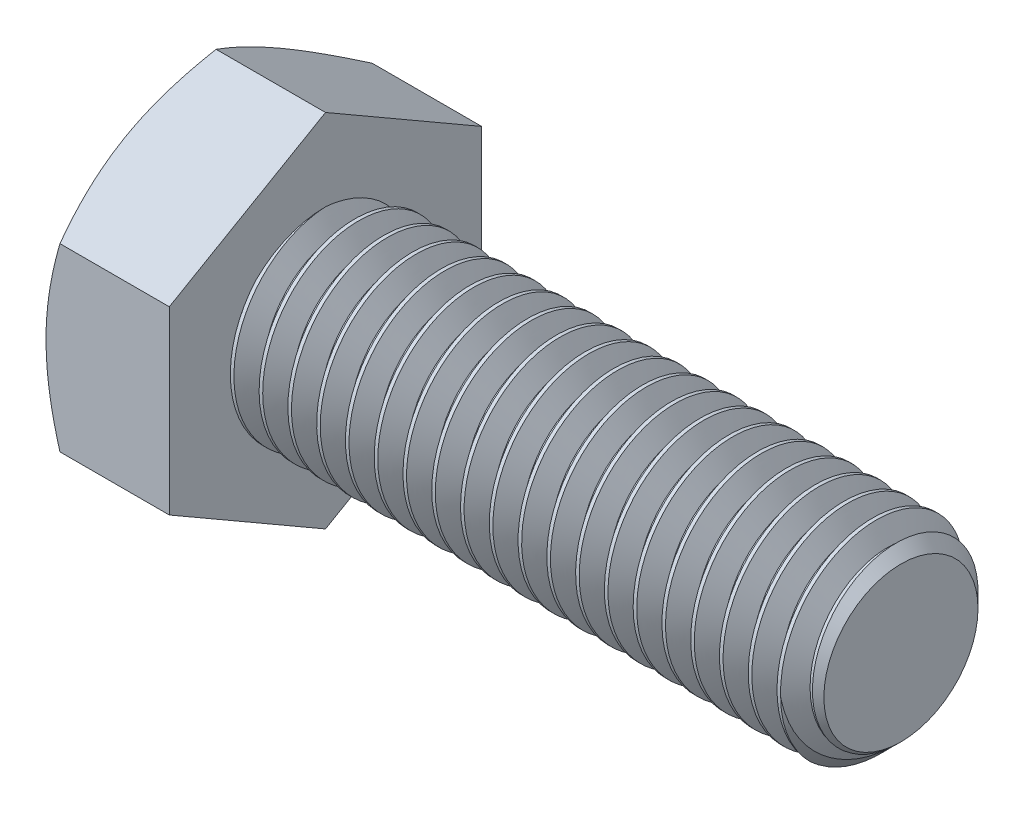
SolidWorks part; units mm, degrees
ref_plane "Front Plane" through (0, 0, 0) normal (0, 0, 1) x (1, 0, 0)
ref_plane "Top Plane" through (0, 0, 0) normal (0, 1, 0) x (1, 0, 0)
ref_plane "Right Plane" through (0, 0, 0) normal (1, 0, 0) x (0, 0, -1)
sketch "Sketch1" plane through (0, 0, 0) normal (0, 0, 1) x (1, 0, 0)
  line L0 (-21.25, 0) -> (21.25, 0) construction
  line L1 (-13.75, 9.5) -> (-13.75, -9.5) construction
  line L2 (-21.25, 9.5) -> (-21.25, -9.5) construction
  line L3 (21.25, 6) -> (21.25, -6) construction
  point P8 (15.125, -6)
  dimension "Thread Dia" = 12
  dimension "Hex" = 19
  dimension "Head Ht" = 7.5
  dimension "Length" = 35
  dimension "D1" = 6.125
ref_plane "Plane2" through (21.25, 0, 0) normal (1, 0, 0) x (0, 0, -1)
sketch "Sketch2" plane through (21.25, 0, 0) normal (1, 0, 0) x (0, 0, -1)
  circle A0 centre (0, 0) radius 6
extrude "Boss-Extrude1" add sketch "Sketch2" against normal up to vertex (35 mm away) up to point (-13.75, -9.5, 0)
sketch "Sketch4" plane through (21.25, 0, 0) normal (1, 0, 0) x (0, 0, -1)
  circle A1 centre (0, 0) radius 6
  circle A2 centre (0, 0) radius 6
  dimension "D1" = 0
curve "Helix/Spiral1" pitch 1.75 height 36.75 turns 21 parameters "Pitch"=1.75
chamfer "Chamfer1" distance 1.3125 angle 45 1 edges at (21.25, 0, -6)
sketch "Sketch5" plane through (0, 0, 0) normal (0, 0, 1) x (1, 0, 0)
  line L0 (21.25, 6) -> (21.9063, 4.8633)
  line L1 (21.9063, 4.8633) -> (22.125, 4.8633)
  line L2 (22.125, 4.8633) -> (22.7813, 6)
  line L3 (21.25, 6) -> (22.7813, 6)
  line L4 (22.0156, 4.8633) -> (22.0156, 6) construction
  line L5 (21.5781, 5.4317) -> (22.4531, 5.4317) construction
  line L6 (21.25, -6) -> (21.25, 6) construction
  dimension "D1" = 60
  dimension "D2" = 0.2188
  dimension "D3" = 0.875
sweep "Cut-Sweep1" cut profiles "Sketch5" path "Helix/Spiral1" align with end faces yes
sketch "Sketch3" plane through (-13.75, 0, 0) normal (-1, 0, 0) x (0, 0, 1)
  line L0 (0, 9.5) -> (0, -9.5) construction
  line L1 (-9.5, -5.4848) -> (0, -10.9697)
  line L2 (0, -10.9697) -> (9.5, -5.4848)
  line L3 (9.5, -5.4848) -> (9.5, 5.4848)
  line L4 (9.5, 5.4848) -> (0, 10.9697)
  line L5 (0, 10.9697) -> (-9.5, 5.4848)
  line L6 (-9.5, 5.4848) -> (-9.5, -5.4848)
  circle A0 centre (0, 0) radius 9.5 construction
extrude "Boss-Extrude2" add sketch "Sketch3" along normal up to vertex (7.5 mm away) up to point (-21.25, -9.5, 0)
sketch "Sketch6" plane through (-21.25, 0, 0) normal (-1, 0, 0) x (0, 0, 1)
  circle A0 centre (0, 0) radius 9.5 construction
  circle A1 centre (0, 0) radius 9.5
extrude "Cut-Extrude1" cut sketch "Sketch6" against normal through all draft 60 flip side to cut
sketch "Sketch7" plane through (-21.25, 0, 0) normal (-1, 0, 0) x (0, 0, 1)
  line L0 (0, 0) -> (0, 9.5) construction
  line L2 (0, 9.5) -> (0, -9.5) construction
  line L3 (-8.2272, 4.75) -> (8.2272, 4.75) construction
  circle A1 centre (0, 0) radius 9.5 construction
  text T0 "10.9\r\n" font "Arial" height in points 28
  point P8 (0, 4.75)
equation "\"D2@Sketch5\" = \"Pitch@Helix/Spiral1\"*.125"
equation "\"D3@Sketch5\" = \"Pitch@Helix/Spiral1\"*.50"
equation "\"D3@Helix/Spiral1\" = \"Length@Sketch1\"+\"Pitch@Helix/Spiral1\""
equation "\"D1@Chamfer1\" = \"Pitch@Helix/Spiral1\"*.750"
equation "\"D1@Sketch1\" = \"Pitch@Helix/Spiral1\"*3.50"
